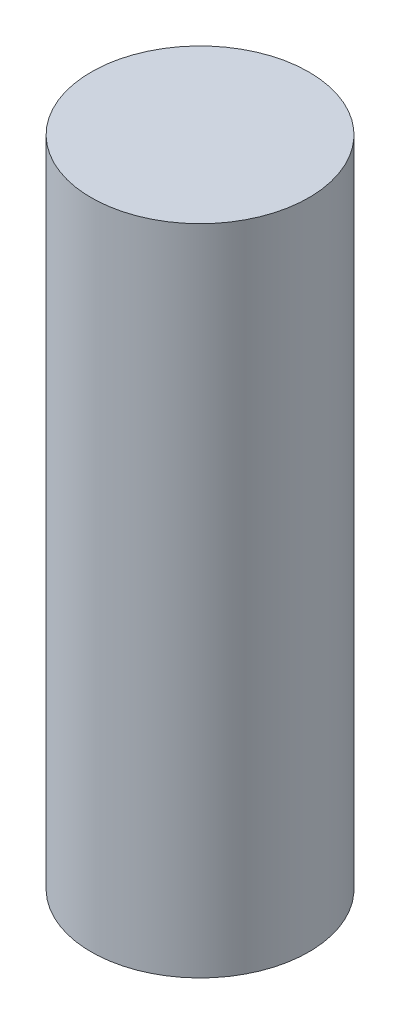
SolidWorks part; units mm, degrees
ref_plane "Front Plane" through (0, 0, 0) normal (0, 0, 1) x (1, 0, 0)
ref_plane "Top Plane" through (0, 0, 0) normal (0, 1, 0) x (1, 0, 0)
ref_plane "Right Plane" through (0, 0, 0) normal (1, 0, 0) x (0, 0, -1)
sketch "Sketch1" plane through (0, 0, 0) normal (0, 1, 0) x (1, 0, 0)
  circle A0 centre (0, 0) radius 1.5875
  dimension "D1" = 3.175
extrude "Boss-Extrude1" add sketch "Sketch1" along normal blind 9.525
equation "\"R\"= 1.5in'radius of rotor"
equation "\"E\"= .125in'eccentricity"
equation "\"R_r\"= .125in'radius of roller"
equation "\"N\"= 14'number of rollers"
equation "\"R_o\"= .2in'output disk pin diameter"
equation "\"D1@Sketch1\"=\"R_r\""
